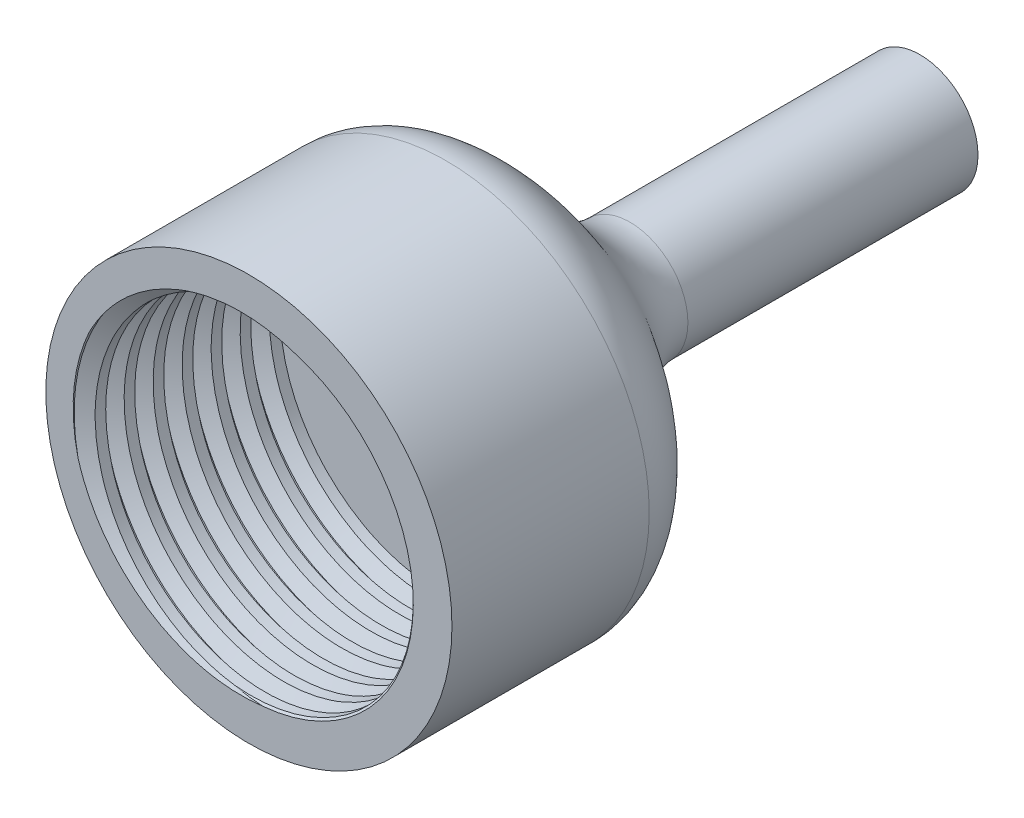
SolidWorks part; units mm, degrees
ref_plane "Front Plane" through (0, 0, 0) normal (0, 0, 1) x (1, 0, 0)
ref_plane "Top Plane" through (0, 0, 0) normal (0, 1, 0) x (1, 0, 0)
ref_plane "Right Plane" through (0, 0, 0) normal (1, 0, 0) x (0, 0, -1)
sketch "Sketch2" plane through (0, 0, 0) normal (0, 1, 0) x (1, 0, 0)
  line L0 (3, 19.7) -> (3, 15.7) construction
  line L1 (0, 34.7) -> (3, 34.7)
  line L2 (3, 34.7) -> (3, 19.7)
  line L4 (10.5, 10.2) -> (10.5, 0)
  line L5 (10.5, 0) -> (0, 0)
  line L6 (0, 0) -> (0, 34.7)
  line L7 (3, 15.7) -> (10.5, 14.2) construction
  line L8 (10.5, 14.2) -> (10.5, 10.2) construction
  spline S0 degree 3 poles (3, 19.7) (3, 15.7) (10.5, 14.2) (10.5, 10.2) knots 0 0 0 0 1 1 1 1
  dimension "D1" = 4
  dimension "D2" = 4
  dimension "D3" = 10.2
  dimension "D4" = 1.5
  dimension "D5" = 15
  dimension "D6" = 3
  dimension "D7" = 10.5
revolve "Body" add sketch "Sketch2" angle 360 about L6
sketch "Sketch3" plane through (0, 0, 0) normal (0, 0, 1) x (1, 0, 0)
  circle A0 centre (0, 0) radius 8.4
  dimension "D1" = 16.8
extrude "Thread Hole" cut sketch "Sketch3" against normal blind 10
thread "Thread" pitch 1.27 method cut trim with end face yes profile "Thread Profile1" start angle 0, offset 2, length 0, pitch 1.5, diameter 16.8
ref_plane "Plane1" through (-8.4, 0, 2) normal (0, -1, 0) x (-1, 0, 0)
sketch "Thread Profile1" plane through (-8.4, 0, 2) normal (0, -1, 0) x (-1, 0, 0)
  line L0 (0, 0) -> (0, 1.27) construction
  line L1 (0, 0) -> (0.6874, 0.3969)
  line L2 (0.6874, 0.3969) -> (0.6874, 0.5556)
  line L3 (0.6874, 0.5556) -> (0, 0.9525)
  line L4 (0.6874, 0.4762) -> (0, 0.4762) construction
  line L11 (0, 0) -> (0, 0.9525)
  point P2 (0, 0)
  dimension "Pitch" = 1.27
  dimension "Profile_Angle" = 60
  dimension "Profile_Land" = 0.1588
  dimension "Profile_Height" = 0.6874
sketch "Sketch6" plane through (0, 0, -34.7) normal (0, 0, -1) x (-1, 0, 0)
  circle A0 centre (0, 0) radius 1.875
  dimension "D1" = 3.75
extrude "Cable Hole" cut sketch "Sketch6" against normal through all
sketch "Sketch7" plane through (0, 0, 0) normal (0, 1, 0) x (1, 0, 0)
  line L0 (0, 8.5) -> (-12, -3.5)
  line L1 (-12, -3.5) -> (0, -3.5)
  line L2 (0, -3.5) -> (0, 8.5)
  dimension "D1" = 12
  dimension "D2" = 45
  dimension "D3" = 3.5
revolve "Thread Chamfer" cut sketch "Sketch7" angle 360 about L2
chamfer "Chamfer1" distance 0.5 angle 45 1 edges at (-1.875, 0, -34.7)
fillet "Chamfer2" radius 1 1 edges at (1.875, 0, -10) profile chamfer
